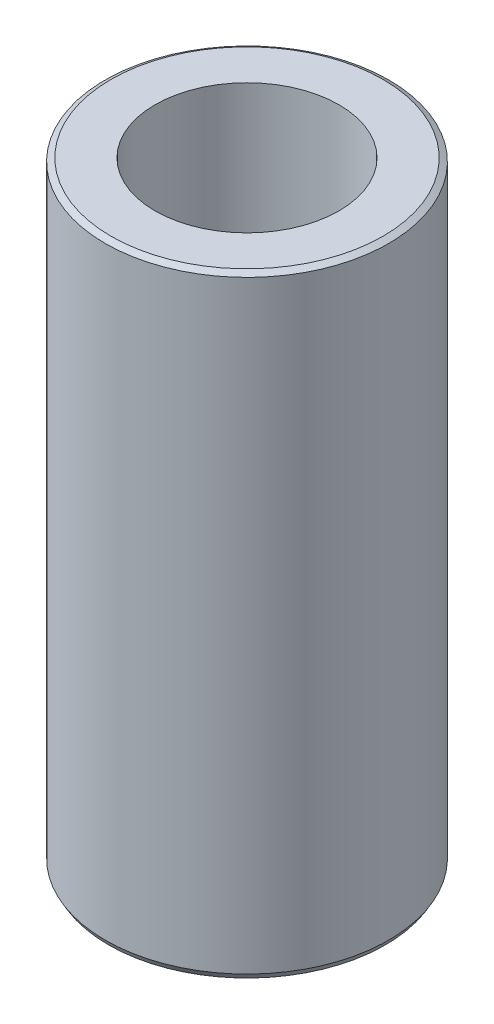
SolidWorks part; units mm, degrees
ref_plane "Front Plane" through (0, 0, 0) normal (0, 0, 1) x (1, 0, 0)
ref_plane "Top Plane" through (0, 0, 0) normal (0, 1, 0) x (1, 0, 0)
ref_plane "Right Plane" through (0, 0, 0) normal (1, 0, 0) x (0, 0, -1)
sketch "Sketch1" plane through (0, 0, 0) normal (0, 1, 0) x (1, 0, 0)
  circle A0 centre (0, 0) radius 50
  dimension "SHAFT_OD" = 100
extrude "Boss-Extrude1" add sketch "Sketch1" along normal blind 216.0859
sketch "Sketch2" plane through (0, 0, 0) normal (0, 1, 0) x (1, 0, 0)
  circle A0 centre (0, 0) radius 32.4468
  dimension "BORE_D" = 64.8936
extrude "Cut-Extrude1" cut sketch "Sketch2" along normal through all
chamfer "Chamfer1" distance 1.1821 angle 60 2 edges at (0, 216.0859, 50) (0, 0, 50) first distance on face at (0, 216.0859, 50) first distance on face at (0, 0, 32.4468)
